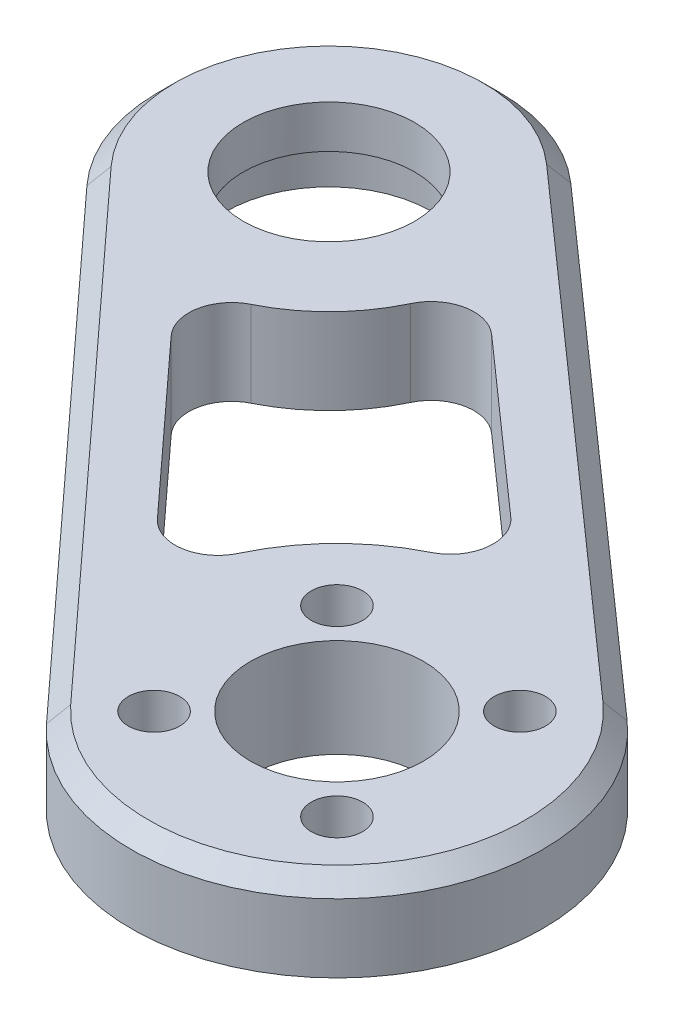
SolidWorks part; units mm, degrees
material "PLA Infill"
ref_plane "Front Plane" through (0, 0, 0) normal (0, 0, 1) x (1, 0, 0)
ref_plane "Top Plane" through (0, 0, 0) normal (0, 1, 0) x (1, 0, 0)
ref_plane "Right Plane" through (0, 0, 0) normal (1, 0, 0) x (0, 0, -1)
sketch "Sketch1" plane through (0, 0, 0) normal (0, 1, 0) x (1, 0, 0)
  line L0 (0, 0) -> (55, 54.0672) construction
  line L1 (55, 54.0672) -> (-55, 54.0672) construction
  line L2 (-55, 54.0672) -> (0, 0) construction
  line L3 (-69.7415, 40.551) -> (-17.6898, -16.2194)
  line L4 (-41.7379, 69.0378) -> (15.9145, 17.9646)
  line L5 (-47.6255, 28.2677) -> (-29.9271, 8.9649)
  line L6 (-29.0781, 47.135) -> (-9.4754, 29.7694)
  circle A0 centre (0, 0) radius 10.1
  circle A1 centre (-55, 54.0672) radius 10
  circle A2 centre (0, 0) radius 24 construction
  circle A3 centre (-55, 54.0672) radius 20 construction
  arc A4 (-69.7415, 40.551) -> (-41.7379, 69.0378) centre (-55, 54.0672) cw
  arc A5 (-17.6898, -16.2194) -> (15.9145, 17.9646) centre (0, 0) ccw
  arc A6 (-46.1521, 36.1308) -> (-36.9149, 45.5274) centre (-55, 54.0672) ccw
  arc A7 (-21.7173, 10.2157) -> (-10.5856, 21.5394) centre (0, 0) cw
  arc A8 (-29.9271, 8.9649) -> (-21.7173, 10.2157) centre (-26.2417, 12.3439) ccw
  arc A9 (-9.4754, 29.7694) -> (-10.5856, 21.5394) centre (-12.7909, 26.0268) cw
  arc A10 (-29.0781, 47.135) -> (-36.9149, 45.5274) centre (-32.3936, 43.3924) ccw
  arc A11 (-47.6255, 28.2677) -> (-46.1521, 36.1308) centre (-43.9401, 31.6467) cw
  point P22 (-23.8825, 2.3723)
  point P25 (-2.7804, 23.8384)
  point P28 (-35.0663, 52.4399)
  point P31 (-53.032, 34.1643)
  dimension "D3" = 20.2
  dimension "D4" = 20
  dimension "D5" = 48
  dimension "D6" = 40
  dimension "D9" = 5
  dimension "D1" = 77.125
  dimension "D2" = 110
  dimension "D7" = 8
  dimension "D8" = 8
extrude "Main Body" add sketch "Sketch1" along normal blind 10
sketch "Sketch2" plane through (0, 0, 0) normal (0, -1, 0) x (1, 0, 0)
  circle A0 centre (-55, -54.0672) radius 10 construction
  circle A1 centre (-55, -54.0672) radius 10 construction
  circle A2 centre (-55, -54.0672) radius 12
  dimension "D1" = 24
extrude "Bearing Recess" cut sketch "Sketch2" against normal blind 5
sketch "Sketch3" plane through (0, 0, 0) normal (0, -1, 0) x (1, 0, 0)
  circle A0 centre (0, 0) radius 21.5
  circle A1 centre (0, 0) radius 10.1
  circle A2 centre (0, 0) radius 10.1 construction
  dimension "D1" = 43
extrude "Standoff Section" add sketch "Sketch3" along normal blind 1.5
sketch "Sketch4" plane through (0, -1.5, 0) normal (0, -1, 0) x (1, 0, 0)
  line L0 (0, 0) -> (50000, 0) construction
  line L1 (55, -54.0672) -> (-55, -54.0672) construction
  line L2 (-10.6773, 10.6773) -> (0, 0) construction
  circle A0 centre (-10.6773, 10.6773) radius 3
  circle A2 centre (10.6773, 10.6773) radius 3
  circle A3 centre (10.6773, -10.6773) radius 3
  circle A4 centre (-10.6773, -10.6773) radius 3
  dimension "D1" = 6
  dimension "D2" = 15.1
  dimension "D3" = 45
  dimension "D4" = 4
extrude "M6 Bolt holes" cut sketch "Sketch4" against normal through all
chamfer "Chamfer1" distance 2 angle 45 4 edges at (17.1151, 10, 16.8248) (-12.9117, 10, -43.5012) (-43.7157, 10, -12.1658) (-69.2626, 10, -68.0879)
